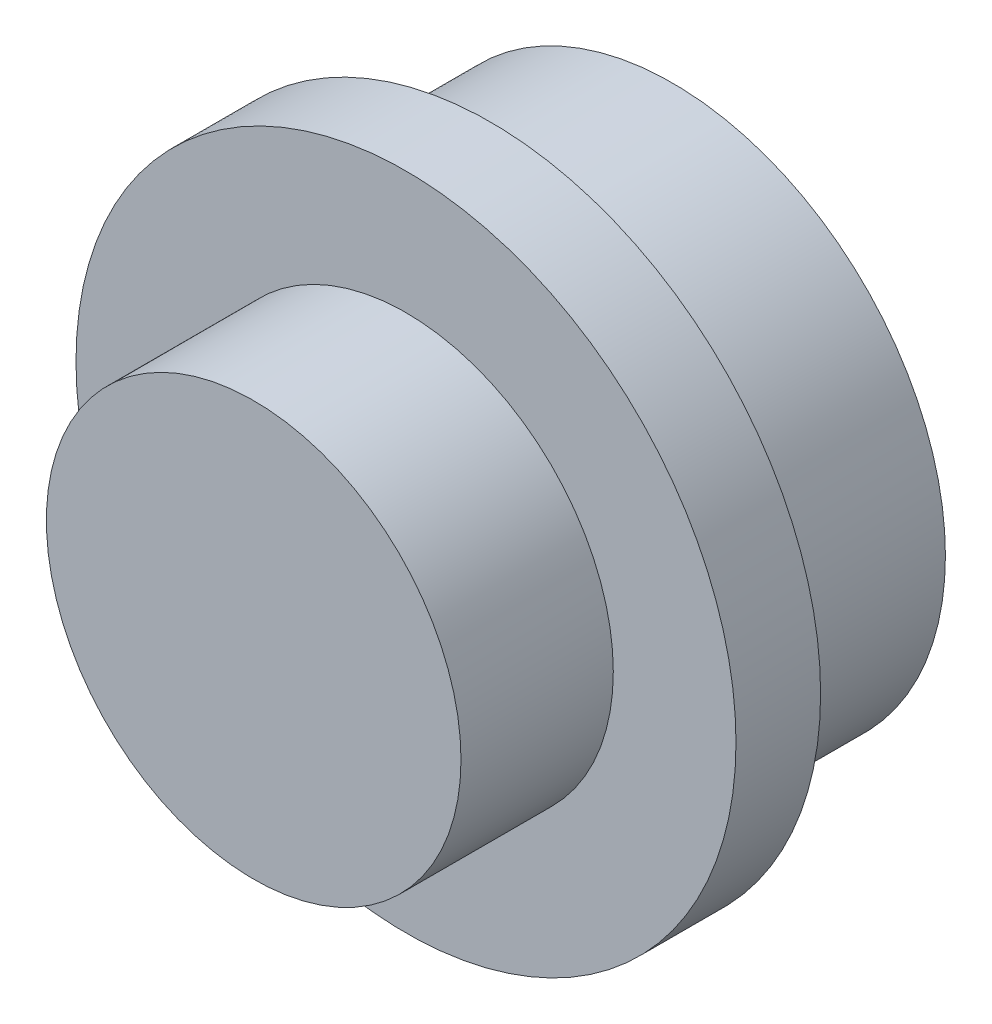
SolidWorks part; units mm, degrees
ref_plane "Front Plane" through (0, 0, 0) normal (0, 0, 1) x (1, 0, 0)
ref_plane "Top Plane" through (0, 0, 0) normal (0, 1, 0) x (1, 0, 0)
ref_plane "Right Plane" through (0, 0, 0) normal (1, 0, 0) x (0, 0, -1)
sketch "Sketch1" plane through (0, 0, 0) normal (0, 0, 1) x (1, 0, 0)
  circle A0 centre (0, 0) radius 3.9
  dimension "D1" = 7.8
extrude "Boss-Extrude1" add sketch "Sketch1" against normal blind 1
sketch "Sketch2" plane through (0, 0, 0) normal (0, 0, 1) x (1, 0, 0)
  circle A0 centre (0, 0) radius 2.45
  dimension "D1" = 4.9
extrude "Boss-Extrude2" add sketch "Sketch2" along normal blind 1.8
shell "Shell1" thickness 1.5 removed face at (3.9, 0, -1)
sketch "Sketch3" plane through (0, 0, -1) normal (0, 0, -1) x (-1, 0, 0)
  circle A0 centre (0, 0) radius 2.345
  circle A1 centre (0, 0) radius 3.225
  dimension "D1" = 6.45
  dimension "D2" = 4.69
extrude "Boss-Extrude3" add sketch "Sketch3" along normal blind 2.15
